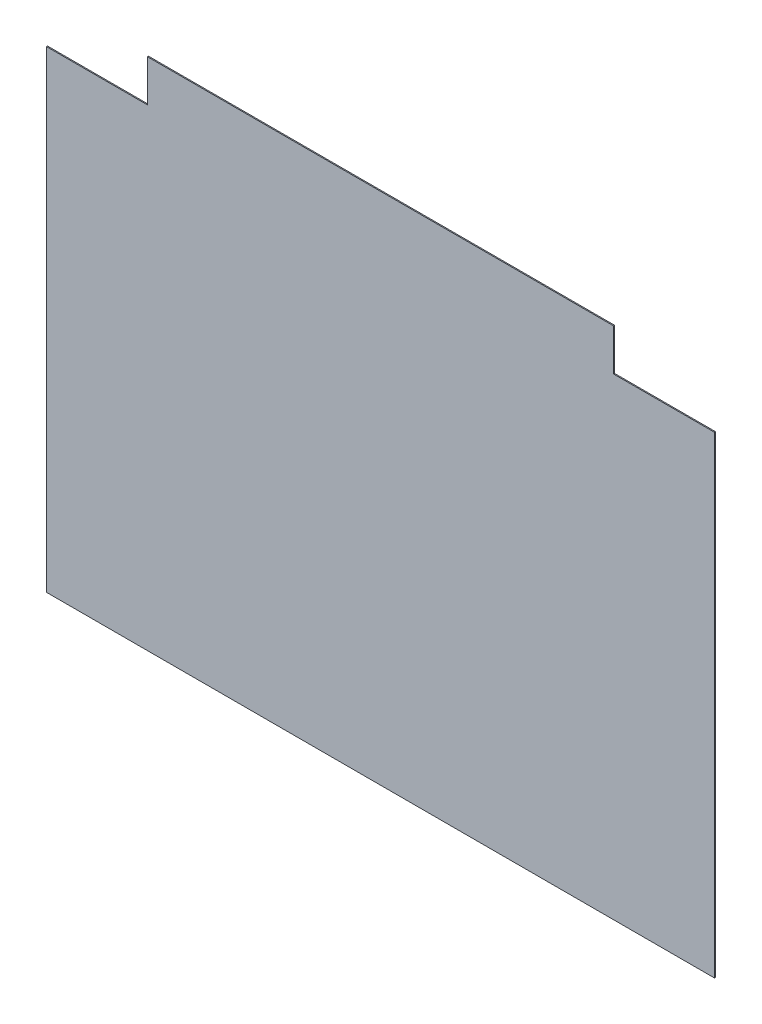
SolidWorks part; units mm, degrees
material "1.0037 (S235JR)"
ref_plane "Front Plane" through (0, 0, 0) normal (0, 0, 1) x (1, 0, 0)
ref_plane "Top Plane" through (0, 0, 0) normal (0, 1, 0) x (1, 0, 0)
ref_plane "Right Plane" through (0, 0, 0) normal (1, 0, 0) x (0, 0, -1)
sketch "Sketch1" plane through (0, 0, 0) normal (0, 0, 1) x (1, 0, 0)
  line L1 (-480.5, 0) -> (480.5, 0)
  line L2 (-480.5, 0) -> (-480.5, 740)
  line L3 (-480.5, 740) -> (480.5, 740)
  line L4 (480.5, 0) -> (480.5, 740)
  line L7 (0, 740) -> (0, 0) construction
  dimension "D1" = 961
  dimension "D6" = 740
base flange "Base-Flange1" sketch "Sketch1" thickness 1.5 reverse thickness direction no parameters "D1"=0.7366
sketch "Sketch2" plane through (0, 0, 0) normal (0, 0, 1) x (1, 0, 0)
  line L1 (-480.5, 740) -> (-335.5, 740)
  line L2 (-480.5, 740) -> (-480.5, 680)
  line L3 (-480.5, 680) -> (-335.5, 680)
  line L4 (-335.5, 740) -> (-335.5, 680)
  dimension "D1" = 145
  dimension "D2" = 60
extrude "Cut-Extrude1" cut sketch "Sketch2" against normal up to next normal cut yes
mirror "Mirror1" about plane through (0, 0, 0) normal (1, 0, 0) of "Cut-Extrude1"
sketch "Bend-Lines1" [suppressed] plane through (0, 0, 0) normal (0, 1, 0) x (1, 0, 0)
sketch "Bounding-Box1" [suppressed] plane through (0, 0, 0) normal (0, 1, 0) x (1, 0, 0)
sheet metal parameters "Sheet-Metal1" thickness 1.5 parameters "D1"=0.7366
flat pattern "Flat-Pattern1" [suppressed]
sketch "Bend-Lines2" plane through (0, 0, 0) normal (0, 1, 0) x (1, 0, 0)
sketch3d "Bounding-Box2" [suppressed]
  line L0 (0, 0, 0) -> (958, 0, 0) construction
  line L1 (0, 740, 0) -> (958, 740, 0) construction
  line L2 (0, 0, 0) -> (0, 740, 0) construction
  line L3 (958, 0, 0) -> (958, 740, 0) construction
sheet metal parameters "Sheet-Metal2" thickness 1.5 parameters "D1"=0.7366
flat pattern "Flat-Pattern1"
sketch "Bend-Lines2" plane through (0, 0, 0) normal (0, 1, 0) x (1, 0, 0)
sketch3d "Bounding-Box2" [suppressed]
  line L0 (-479, 0, 0) -> (479, 0, 0) construction
  line L1 (-479, 740, 0) -> (479, 740, 0) construction
  line L2 (-479, 0, 0) -> (-479, 740, 0) construction
  line L3 (479, 0, 0) -> (479, 740, 0) construction
sheet metal parameters "Sheet-Metal3" thickness 1.5 parameters "D1"=0.7366
flat pattern "Flat-Pattern1"
sketch "Bend-Lines2" plane through (0, 0, 0) normal (0, 1, 0) x (1, 0, 0)
sketch3d "Bounding-Box2" [suppressed]
  line L0 (-480.5, 0, 0) -> (480.5, 0, 0) construction
  line L1 (-480.5, 740, 0) -> (480.5, 740, 0) construction
  line L2 (-480.5, 0, 0) -> (-480.5, 740, 0) construction
  line L3 (480.5, 0, 0) -> (480.5, 740, 0) construction
